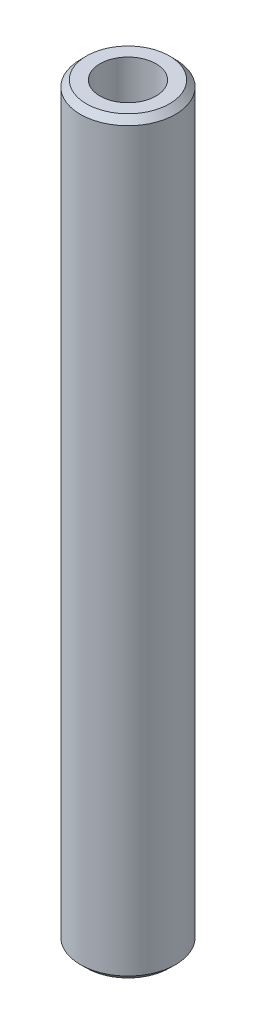
SolidWorks part; units mm, degrees
ref_plane "Front Plane" through (0, 0, 0) normal (0, 0, 1) x (1, 0, 0)
ref_plane "Top Plane" through (0, 0, 0) normal (0, 1, 0) x (1, 0, 0)
ref_plane "Right Plane" through (0, 0, 0) normal (1, 0, 0) x (0, 0, -1)
sketch "Sketch1" plane through (0, 0, 0) normal (0, 1, 0) x (1, 0, 0)
  circle A0 centre (0, 0) radius 37.5
  dimension "SHAFT_OD" = 75
extrude "Boss-Extrude1" add sketch "Sketch1" along normal blind 590.7804
sketch "Sketch2" plane through (0, 0, 0) normal (0, 1, 0) x (1, 0, 0)
  circle A0 centre (0, 0) radius 22.1141
  dimension "BORE_D" = 44.2282
extrude "Cut-Extrude1" cut sketch "Sketch2" along normal through all
chamfer "Chamfer1" distance 4.8392 angle 44.411 2 edges at (0, 590.7804, 37.5) (0, 0, 37.5) first distance on face at (0, 590.7804, 37.5) first distance on face at (0, 0, 22.1141)
